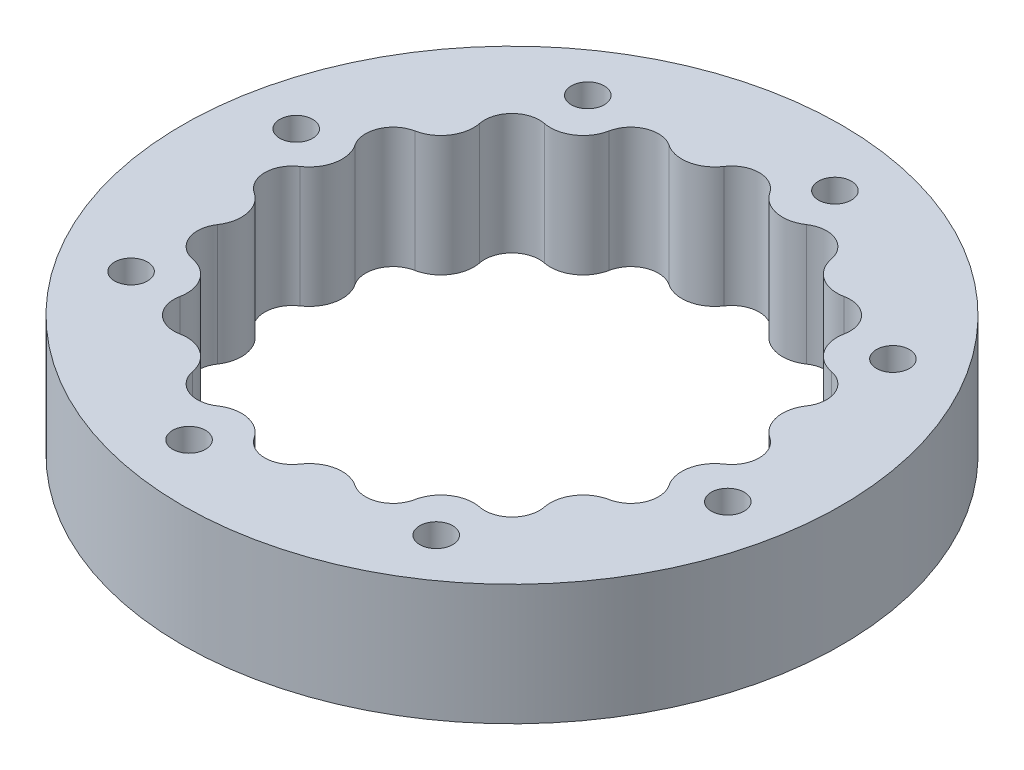
SolidWorks part; units mm, degrees
ref_plane "Front Plane" through (0, 0, 0) normal (0, 0, 1) x (1, 0, 0)
ref_plane "Top Plane" through (0, 0, 0) normal (0, 1, 0) x (1, 0, 0)
ref_plane "Right Plane" through (0, 0, 0) normal (1, 0, 0) x (0, 0, -1)
sketch "Sketch1" plane through (0, 0, 0) normal (0, 1, 0) x (1, 0, 0)
  arc A0 (-31.5919, 24.5347) -> (-34.7568, 19.7981) centre (0, 0) ccw
  arc A1 (4.9902, 39.6875) -> (-4.9902, 39.6875) centre (0, 40) ccw
  arc A2 (19.7981, 34.7568) -> (10.5774, 38.5761) centre (15.3073, 36.9552) ccw
  arc A3 (-31.5919, 24.5347) -> (-34.7568, 19.7981) centre (0, 0) ccw construction
  arc A4 (31.5919, 24.5347) -> (24.5347, 31.5919) centre (28.2843, 28.2843) ccw
  arc A5 (-31.5919, 24.5347) -> (-34.7568, 19.7981) centre (0, 0) ccw construction
  arc A6 (38.5761, 10.5774) -> (34.7568, 19.7981) centre (36.9552, 15.3073) ccw
  arc A7 (-31.5919, 24.5347) -> (-34.7568, 19.7981) centre (0, 0) ccw construction
  arc A8 (39.6875, -4.9902) -> (39.6875, 4.9902) centre (40, 0) ccw
  arc A9 (-31.5919, 24.5347) -> (-34.7568, 19.7981) centre (0, 0) ccw construction
  arc A10 (34.7568, -19.7981) -> (38.5761, -10.5774) centre (36.9552, -15.3073) ccw
  arc A11 (-31.5919, 24.5347) -> (-34.7568, 19.7981) centre (0, 0) ccw construction
  arc A12 (24.5347, -31.5919) -> (31.5919, -24.5347) centre (28.2843, -28.2843) ccw
  arc A13 (-31.5919, 24.5347) -> (-34.7568, 19.7981) centre (0, 0) ccw construction
  arc A14 (10.5774, -38.5761) -> (19.7981, -34.7568) centre (15.3073, -36.9552) ccw
  arc A15 (-31.5919, 24.5347) -> (-34.7568, 19.7981) centre (0, 0) ccw construction
  arc A16 (-4.9902, -39.6875) -> (4.9902, -39.6875) centre (0, -40) ccw
  arc A17 (-31.5919, 24.5347) -> (-34.7568, 19.7981) centre (0, 0) ccw construction
  arc A18 (-19.7981, -34.7568) -> (-10.5774, -38.5761) centre (-15.3073, -36.9552) ccw
  arc A19 (-31.5919, 24.5347) -> (-34.7568, 19.7981) centre (0, 0) ccw construction
  arc A20 (-31.5919, -24.5347) -> (-24.5347, -31.5919) centre (-28.2843, -28.2843) ccw
  arc A21 (-31.5919, 24.5347) -> (-34.7568, 19.7981) centre (0, 0) ccw construction
  arc A22 (-38.5761, -10.5774) -> (-34.7568, -19.7981) centre (-36.9552, -15.3073) ccw
  arc A23 (-31.5919, 24.5347) -> (-34.7568, 19.7981) centre (0, 0) ccw construction
  arc A24 (-39.6875, 4.9902) -> (-39.6875, -4.9902) centre (-40, 0) ccw
  arc A25 (-31.5919, 24.5347) -> (-34.7568, 19.7981) centre (0, 0) ccw construction
  arc A26 (-34.7568, 19.7981) -> (-38.5761, 10.5774) centre (-36.9552, 15.3073) ccw
  arc A27 (-31.5919, 24.5347) -> (-34.7568, 19.7981) centre (0, 0) ccw construction
  arc A28 (-24.5347, 31.5919) -> (-31.5919, 24.5347) centre (-28.2843, 28.2843) ccw
  arc A29 (-31.5919, 24.5347) -> (-34.7568, 19.7981) centre (0, 0) ccw construction
  arc A30 (-10.5774, 38.5761) -> (-19.7981, 34.7568) centre (-15.3073, 36.9552) ccw
  arc A31 (-31.5919, 24.5347) -> (-34.7568, 19.7981) centre (0, 0) ccw construction
  circle A32 centre (0, 0) radius 60
  arc A33 (-19.7981, 34.7568) -> (-24.5347, 31.5919) centre (0, 0) ccw
  arc A34 (-19.7981, 34.7568) -> (-24.5347, 31.5919) centre (0, 0) ccw construction
  arc A35 (-19.7981, 34.7568) -> (-24.5347, 31.5919) centre (0, 0) ccw construction
  arc A36 (-19.7981, 34.7568) -> (-24.5347, 31.5919) centre (0, 0) ccw construction
  arc A37 (-19.7981, 34.7568) -> (-24.5347, 31.5919) centre (0, 0) ccw construction
  arc A38 (-19.7981, 34.7568) -> (-24.5347, 31.5919) centre (0, 0) ccw construction
  arc A39 (-19.7981, 34.7568) -> (-24.5347, 31.5919) centre (0, 0) ccw construction
  arc A40 (-19.7981, 34.7568) -> (-24.5347, 31.5919) centre (0, 0) ccw construction
  arc A41 (-19.7981, 34.7568) -> (-24.5347, 31.5919) centre (0, 0) ccw construction
  arc A42 (-19.7981, 34.7568) -> (-24.5347, 31.5919) centre (0, 0) ccw construction
  arc A43 (-19.7981, 34.7568) -> (-24.5347, 31.5919) centre (0, 0) ccw construction
  arc A44 (-19.7981, 34.7568) -> (-24.5347, 31.5919) centre (0, 0) ccw construction
  arc A45 (-19.7981, 34.7568) -> (-24.5347, 31.5919) centre (0, 0) ccw construction
  arc A46 (-19.7981, 34.7568) -> (-24.5347, 31.5919) centre (0, 0) ccw construction
  arc A47 (-19.7981, 34.7568) -> (-24.5347, 31.5919) centre (0, 0) ccw construction
  arc A48 (-19.7981, 34.7568) -> (-24.5347, 31.5919) centre (0, 0) ccw construction
  arc A49 (-4.9902, 39.6875) -> (-10.5774, 38.5761) centre (0, 0) ccw
  arc A50 (-4.9902, 39.6875) -> (-10.5774, 38.5761) centre (0, 0) ccw construction
  arc A51 (-4.9902, 39.6875) -> (-10.5774, 38.5761) centre (0, 0) ccw construction
  arc A52 (-4.9902, 39.6875) -> (-10.5774, 38.5761) centre (0, 0) ccw construction
  arc A53 (-4.9902, 39.6875) -> (-10.5774, 38.5761) centre (0, 0) ccw construction
  arc A54 (-4.9902, 39.6875) -> (-10.5774, 38.5761) centre (0, 0) ccw construction
  arc A55 (-4.9902, 39.6875) -> (-10.5774, 38.5761) centre (0, 0) ccw construction
  arc A56 (-4.9902, 39.6875) -> (-10.5774, 38.5761) centre (0, 0) ccw construction
  arc A57 (-4.9902, 39.6875) -> (-10.5774, 38.5761) centre (0, 0) ccw construction
  arc A58 (-4.9902, 39.6875) -> (-10.5774, 38.5761) centre (0, 0) ccw construction
  arc A59 (-4.9902, 39.6875) -> (-10.5774, 38.5761) centre (0, 0) ccw construction
  arc A60 (-4.9902, 39.6875) -> (-10.5774, 38.5761) centre (0, 0) ccw construction
  arc A61 (-4.9902, 39.6875) -> (-10.5774, 38.5761) centre (0, 0) ccw construction
  arc A62 (-4.9902, 39.6875) -> (-10.5774, 38.5761) centre (0, 0) ccw construction
  arc A63 (-4.9902, 39.6875) -> (-10.5774, 38.5761) centre (0, 0) ccw construction
  arc A64 (-4.9902, 39.6875) -> (-10.5774, 38.5761) centre (0, 0) ccw construction
  arc A65 (10.5774, 38.5761) -> (4.9902, 39.6875) centre (0, 0) ccw
  arc A66 (10.5774, 38.5761) -> (4.9902, 39.6875) centre (0, 0) ccw construction
  arc A67 (10.5774, 38.5761) -> (4.9902, 39.6875) centre (0, 0) ccw construction
  arc A68 (10.5774, 38.5761) -> (4.9902, 39.6875) centre (0, 0) ccw construction
  arc A69 (10.5774, 38.5761) -> (4.9902, 39.6875) centre (0, 0) ccw construction
  arc A70 (10.5774, 38.5761) -> (4.9902, 39.6875) centre (0, 0) ccw construction
  arc A71 (10.5774, 38.5761) -> (4.9902, 39.6875) centre (0, 0) ccw construction
  arc A72 (10.5774, 38.5761) -> (4.9902, 39.6875) centre (0, 0) ccw construction
  arc A73 (10.5774, 38.5761) -> (4.9902, 39.6875) centre (0, 0) ccw construction
  arc A74 (10.5774, 38.5761) -> (4.9902, 39.6875) centre (0, 0) ccw construction
  arc A75 (10.5774, 38.5761) -> (4.9902, 39.6875) centre (0, 0) ccw construction
  arc A76 (10.5774, 38.5761) -> (4.9902, 39.6875) centre (0, 0) ccw construction
  arc A77 (10.5774, 38.5761) -> (4.9902, 39.6875) centre (0, 0) ccw construction
  arc A78 (10.5774, 38.5761) -> (4.9902, 39.6875) centre (0, 0) ccw construction
  arc A79 (10.5774, 38.5761) -> (4.9902, 39.6875) centre (0, 0) ccw construction
  arc A80 (10.5774, 38.5761) -> (4.9902, 39.6875) centre (0, 0) ccw construction
  arc A81 (24.5347, 31.5919) -> (19.7981, 34.7568) centre (0, 0) ccw
  arc A82 (24.5347, 31.5919) -> (19.7981, 34.7568) centre (0, 0) ccw construction
  arc A83 (24.5347, 31.5919) -> (19.7981, 34.7568) centre (0, 0) ccw construction
  arc A84 (24.5347, 31.5919) -> (19.7981, 34.7568) centre (0, 0) ccw construction
  arc A85 (24.5347, 31.5919) -> (19.7981, 34.7568) centre (0, 0) ccw construction
  arc A86 (24.5347, 31.5919) -> (19.7981, 34.7568) centre (0, 0) ccw construction
  arc A87 (24.5347, 31.5919) -> (19.7981, 34.7568) centre (0, 0) ccw construction
  arc A88 (24.5347, 31.5919) -> (19.7981, 34.7568) centre (0, 0) ccw construction
  arc A89 (24.5347, 31.5919) -> (19.7981, 34.7568) centre (0, 0) ccw construction
  arc A90 (24.5347, 31.5919) -> (19.7981, 34.7568) centre (0, 0) ccw construction
  arc A91 (24.5347, 31.5919) -> (19.7981, 34.7568) centre (0, 0) ccw construction
  arc A92 (24.5347, 31.5919) -> (19.7981, 34.7568) centre (0, 0) ccw construction
  arc A93 (24.5347, 31.5919) -> (19.7981, 34.7568) centre (0, 0) ccw construction
  arc A94 (24.5347, 31.5919) -> (19.7981, 34.7568) centre (0, 0) ccw construction
  arc A95 (24.5347, 31.5919) -> (19.7981, 34.7568) centre (0, 0) ccw construction
  arc A96 (24.5347, 31.5919) -> (19.7981, 34.7568) centre (0, 0) ccw construction
  arc A97 (34.7568, 19.7981) -> (31.5919, 24.5347) centre (0, 0) ccw
  arc A98 (34.7568, 19.7981) -> (31.5919, 24.5347) centre (0, 0) ccw construction
  arc A99 (34.7568, 19.7981) -> (31.5919, 24.5347) centre (0, 0) ccw construction
  arc A100 (34.7568, 19.7981) -> (31.5919, 24.5347) centre (0, 0) ccw construction
  arc A101 (34.7568, 19.7981) -> (31.5919, 24.5347) centre (0, 0) ccw construction
  arc A102 (34.7568, 19.7981) -> (31.5919, 24.5347) centre (0, 0) ccw construction
  arc A103 (34.7568, 19.7981) -> (31.5919, 24.5347) centre (0, 0) ccw construction
  arc A104 (34.7568, 19.7981) -> (31.5919, 24.5347) centre (0, 0) ccw construction
  arc A105 (34.7568, 19.7981) -> (31.5919, 24.5347) centre (0, 0) ccw construction
  arc A106 (34.7568, 19.7981) -> (31.5919, 24.5347) centre (0, 0) ccw construction
  arc A107 (34.7568, 19.7981) -> (31.5919, 24.5347) centre (0, 0) ccw construction
  arc A108 (34.7568, 19.7981) -> (31.5919, 24.5347) centre (0, 0) ccw construction
  arc A109 (34.7568, 19.7981) -> (31.5919, 24.5347) centre (0, 0) ccw construction
  arc A110 (34.7568, 19.7981) -> (31.5919, 24.5347) centre (0, 0) ccw construction
  arc A111 (34.7568, 19.7981) -> (31.5919, 24.5347) centre (0, 0) ccw construction
  arc A112 (34.7568, 19.7981) -> (31.5919, 24.5347) centre (0, 0) ccw construction
  arc A113 (39.6875, 4.9902) -> (38.5761, 10.5774) centre (0, 0) ccw
  arc A114 (39.6875, 4.9902) -> (38.5761, 10.5774) centre (0, 0) ccw construction
  arc A115 (39.6875, 4.9902) -> (38.5761, 10.5774) centre (0, 0) ccw construction
  arc A116 (39.6875, 4.9902) -> (38.5761, 10.5774) centre (0, 0) ccw construction
  arc A117 (39.6875, 4.9902) -> (38.5761, 10.5774) centre (0, 0) ccw construction
  arc A118 (39.6875, 4.9902) -> (38.5761, 10.5774) centre (0, 0) ccw construction
  arc A119 (39.6875, 4.9902) -> (38.5761, 10.5774) centre (0, 0) ccw construction
  arc A120 (39.6875, 4.9902) -> (38.5761, 10.5774) centre (0, 0) ccw construction
  arc A121 (39.6875, 4.9902) -> (38.5761, 10.5774) centre (0, 0) ccw construction
  arc A122 (39.6875, 4.9902) -> (38.5761, 10.5774) centre (0, 0) ccw construction
  arc A123 (39.6875, 4.9902) -> (38.5761, 10.5774) centre (0, 0) ccw construction
  arc A124 (39.6875, 4.9902) -> (38.5761, 10.5774) centre (0, 0) ccw construction
  arc A125 (39.6875, 4.9902) -> (38.5761, 10.5774) centre (0, 0) ccw construction
  arc A126 (39.6875, 4.9902) -> (38.5761, 10.5774) centre (0, 0) ccw construction
  arc A127 (39.6875, 4.9902) -> (38.5761, 10.5774) centre (0, 0) ccw construction
  arc A128 (39.6875, 4.9902) -> (38.5761, 10.5774) centre (0, 0) ccw construction
  arc A129 (38.5761, -10.5774) -> (39.6875, -4.9902) centre (0, 0) ccw
  arc A130 (38.5761, -10.5774) -> (39.6875, -4.9902) centre (0, 0) ccw construction
  arc A131 (38.5761, -10.5774) -> (39.6875, -4.9902) centre (0, 0) ccw construction
  arc A132 (38.5761, -10.5774) -> (39.6875, -4.9902) centre (0, 0) ccw construction
  arc A133 (38.5761, -10.5774) -> (39.6875, -4.9902) centre (0, 0) ccw construction
  arc A134 (38.5761, -10.5774) -> (39.6875, -4.9902) centre (0, 0) ccw construction
  arc A135 (38.5761, -10.5774) -> (39.6875, -4.9902) centre (0, 0) ccw construction
  arc A136 (38.5761, -10.5774) -> (39.6875, -4.9902) centre (0, 0) ccw construction
  arc A137 (38.5761, -10.5774) -> (39.6875, -4.9902) centre (0, 0) ccw construction
  arc A138 (38.5761, -10.5774) -> (39.6875, -4.9902) centre (0, 0) ccw construction
  arc A139 (38.5761, -10.5774) -> (39.6875, -4.9902) centre (0, 0) ccw construction
  arc A140 (38.5761, -10.5774) -> (39.6875, -4.9902) centre (0, 0) ccw construction
  arc A141 (38.5761, -10.5774) -> (39.6875, -4.9902) centre (0, 0) ccw construction
  arc A142 (38.5761, -10.5774) -> (39.6875, -4.9902) centre (0, 0) ccw construction
  arc A143 (38.5761, -10.5774) -> (39.6875, -4.9902) centre (0, 0) ccw construction
  arc A144 (38.5761, -10.5774) -> (39.6875, -4.9902) centre (0, 0) ccw construction
  arc A145 (31.5919, -24.5347) -> (34.7568, -19.7981) centre (0, 0) ccw
  arc A146 (31.5919, -24.5347) -> (34.7568, -19.7981) centre (0, 0) ccw construction
  arc A147 (31.5919, -24.5347) -> (34.7568, -19.7981) centre (0, 0) ccw construction
  arc A148 (31.5919, -24.5347) -> (34.7568, -19.7981) centre (0, 0) ccw construction
  arc A149 (31.5919, -24.5347) -> (34.7568, -19.7981) centre (0, 0) ccw construction
  arc A150 (31.5919, -24.5347) -> (34.7568, -19.7981) centre (0, 0) ccw construction
  arc A151 (31.5919, -24.5347) -> (34.7568, -19.7981) centre (0, 0) ccw construction
  arc A152 (31.5919, -24.5347) -> (34.7568, -19.7981) centre (0, 0) ccw construction
  arc A153 (31.5919, -24.5347) -> (34.7568, -19.7981) centre (0, 0) ccw construction
  arc A154 (31.5919, -24.5347) -> (34.7568, -19.7981) centre (0, 0) ccw construction
  arc A155 (31.5919, -24.5347) -> (34.7568, -19.7981) centre (0, 0) ccw construction
  arc A156 (31.5919, -24.5347) -> (34.7568, -19.7981) centre (0, 0) ccw construction
  arc A157 (31.5919, -24.5347) -> (34.7568, -19.7981) centre (0, 0) ccw construction
  arc A158 (31.5919, -24.5347) -> (34.7568, -19.7981) centre (0, 0) ccw construction
  arc A159 (31.5919, -24.5347) -> (34.7568, -19.7981) centre (0, 0) ccw construction
  arc A160 (31.5919, -24.5347) -> (34.7568, -19.7981) centre (0, 0) ccw construction
  arc A161 (19.7981, -34.7568) -> (24.5347, -31.5919) centre (0, 0) ccw
  arc A162 (19.7981, -34.7568) -> (24.5347, -31.5919) centre (0, 0) ccw construction
  arc A163 (19.7981, -34.7568) -> (24.5347, -31.5919) centre (0, 0) ccw construction
  arc A164 (19.7981, -34.7568) -> (24.5347, -31.5919) centre (0, 0) ccw construction
  arc A165 (19.7981, -34.7568) -> (24.5347, -31.5919) centre (0, 0) ccw construction
  arc A166 (19.7981, -34.7568) -> (24.5347, -31.5919) centre (0, 0) ccw construction
  arc A167 (19.7981, -34.7568) -> (24.5347, -31.5919) centre (0, 0) ccw construction
  arc A168 (19.7981, -34.7568) -> (24.5347, -31.5919) centre (0, 0) ccw construction
  arc A169 (19.7981, -34.7568) -> (24.5347, -31.5919) centre (0, 0) ccw construction
  arc A170 (19.7981, -34.7568) -> (24.5347, -31.5919) centre (0, 0) ccw construction
  arc A171 (19.7981, -34.7568) -> (24.5347, -31.5919) centre (0, 0) ccw construction
  arc A172 (19.7981, -34.7568) -> (24.5347, -31.5919) centre (0, 0) ccw construction
  arc A173 (19.7981, -34.7568) -> (24.5347, -31.5919) centre (0, 0) ccw construction
  arc A174 (19.7981, -34.7568) -> (24.5347, -31.5919) centre (0, 0) ccw construction
  arc A175 (19.7981, -34.7568) -> (24.5347, -31.5919) centre (0, 0) ccw construction
  arc A176 (19.7981, -34.7568) -> (24.5347, -31.5919) centre (0, 0) ccw construction
  arc A177 (4.9902, -39.6875) -> (10.5774, -38.5761) centre (0, 0) ccw
  arc A178 (4.9902, -39.6875) -> (10.5774, -38.5761) centre (0, 0) ccw construction
  arc A179 (4.9902, -39.6875) -> (10.5774, -38.5761) centre (0, 0) ccw construction
  arc A180 (4.9902, -39.6875) -> (10.5774, -38.5761) centre (0, 0) ccw construction
  arc A181 (4.9902, -39.6875) -> (10.5774, -38.5761) centre (0, 0) ccw construction
  arc A182 (4.9902, -39.6875) -> (10.5774, -38.5761) centre (0, 0) ccw construction
  arc A183 (4.9902, -39.6875) -> (10.5774, -38.5761) centre (0, 0) ccw construction
  arc A184 (4.9902, -39.6875) -> (10.5774, -38.5761) centre (0, 0) ccw construction
  arc A185 (4.9902, -39.6875) -> (10.5774, -38.5761) centre (0, 0) ccw construction
  arc A186 (4.9902, -39.6875) -> (10.5774, -38.5761) centre (0, 0) ccw construction
  arc A187 (4.9902, -39.6875) -> (10.5774, -38.5761) centre (0, 0) ccw construction
  arc A188 (4.9902, -39.6875) -> (10.5774, -38.5761) centre (0, 0) ccw construction
  arc A189 (4.9902, -39.6875) -> (10.5774, -38.5761) centre (0, 0) ccw construction
  arc A190 (4.9902, -39.6875) -> (10.5774, -38.5761) centre (0, 0) ccw construction
  arc A191 (4.9902, -39.6875) -> (10.5774, -38.5761) centre (0, 0) ccw construction
  arc A192 (4.9902, -39.6875) -> (10.5774, -38.5761) centre (0, 0) ccw construction
  arc A193 (-10.5774, -38.5761) -> (-4.9902, -39.6875) centre (0, 0) ccw
  arc A194 (-10.5774, -38.5761) -> (-4.9902, -39.6875) centre (0, 0) ccw construction
  arc A195 (-10.5774, -38.5761) -> (-4.9902, -39.6875) centre (0, 0) ccw construction
  arc A196 (-10.5774, -38.5761) -> (-4.9902, -39.6875) centre (0, 0) ccw construction
  arc A197 (-10.5774, -38.5761) -> (-4.9902, -39.6875) centre (0, 0) ccw construction
  arc A198 (-10.5774, -38.5761) -> (-4.9902, -39.6875) centre (0, 0) ccw construction
  arc A199 (-10.5774, -38.5761) -> (-4.9902, -39.6875) centre (0, 0) ccw construction
  arc A200 (-10.5774, -38.5761) -> (-4.9902, -39.6875) centre (0, 0) ccw construction
  arc A201 (-10.5774, -38.5761) -> (-4.9902, -39.6875) centre (0, 0) ccw construction
  arc A202 (-10.5774, -38.5761) -> (-4.9902, -39.6875) centre (0, 0) ccw construction
  arc A203 (-10.5774, -38.5761) -> (-4.9902, -39.6875) centre (0, 0) ccw construction
  arc A204 (-10.5774, -38.5761) -> (-4.9902, -39.6875) centre (0, 0) ccw construction
  arc A205 (-10.5774, -38.5761) -> (-4.9902, -39.6875) centre (0, 0) ccw construction
  arc A206 (-10.5774, -38.5761) -> (-4.9902, -39.6875) centre (0, 0) ccw construction
  arc A207 (-10.5774, -38.5761) -> (-4.9902, -39.6875) centre (0, 0) ccw construction
  arc A208 (-10.5774, -38.5761) -> (-4.9902, -39.6875) centre (0, 0) ccw construction
  arc A209 (-24.5347, -31.5919) -> (-19.7981, -34.7568) centre (0, 0) ccw
  arc A210 (-24.5347, -31.5919) -> (-19.7981, -34.7568) centre (0, 0) ccw construction
  arc A211 (-24.5347, -31.5919) -> (-19.7981, -34.7568) centre (0, 0) ccw construction
  arc A212 (-24.5347, -31.5919) -> (-19.7981, -34.7568) centre (0, 0) ccw construction
  arc A213 (-24.5347, -31.5919) -> (-19.7981, -34.7568) centre (0, 0) ccw construction
  arc A214 (-24.5347, -31.5919) -> (-19.7981, -34.7568) centre (0, 0) ccw construction
  arc A215 (-24.5347, -31.5919) -> (-19.7981, -34.7568) centre (0, 0) ccw construction
  arc A216 (-24.5347, -31.5919) -> (-19.7981, -34.7568) centre (0, 0) ccw construction
  arc A217 (-24.5347, -31.5919) -> (-19.7981, -34.7568) centre (0, 0) ccw construction
  arc A218 (-24.5347, -31.5919) -> (-19.7981, -34.7568) centre (0, 0) ccw construction
  arc A219 (-24.5347, -31.5919) -> (-19.7981, -34.7568) centre (0, 0) ccw construction
  arc A220 (-24.5347, -31.5919) -> (-19.7981, -34.7568) centre (0, 0) ccw construction
  arc A221 (-24.5347, -31.5919) -> (-19.7981, -34.7568) centre (0, 0) ccw construction
  arc A222 (-24.5347, -31.5919) -> (-19.7981, -34.7568) centre (0, 0) ccw construction
  arc A223 (-24.5347, -31.5919) -> (-19.7981, -34.7568) centre (0, 0) ccw construction
  arc A224 (-24.5347, -31.5919) -> (-19.7981, -34.7568) centre (0, 0) ccw construction
  arc A225 (-34.7568, -19.7981) -> (-31.5919, -24.5347) centre (0, 0) ccw
  arc A226 (-34.7568, -19.7981) -> (-31.5919, -24.5347) centre (0, 0) ccw construction
  arc A227 (-34.7568, -19.7981) -> (-31.5919, -24.5347) centre (0, 0) ccw construction
  arc A228 (-34.7568, -19.7981) -> (-31.5919, -24.5347) centre (0, 0) ccw construction
  arc A229 (-34.7568, -19.7981) -> (-31.5919, -24.5347) centre (0, 0) ccw construction
  arc A230 (-34.7568, -19.7981) -> (-31.5919, -24.5347) centre (0, 0) ccw construction
  arc A231 (-34.7568, -19.7981) -> (-31.5919, -24.5347) centre (0, 0) ccw construction
  arc A232 (-34.7568, -19.7981) -> (-31.5919, -24.5347) centre (0, 0) ccw construction
  arc A233 (-34.7568, -19.7981) -> (-31.5919, -24.5347) centre (0, 0) ccw construction
  arc A234 (-34.7568, -19.7981) -> (-31.5919, -24.5347) centre (0, 0) ccw construction
  arc A235 (-34.7568, -19.7981) -> (-31.5919, -24.5347) centre (0, 0) ccw construction
  arc A236 (-34.7568, -19.7981) -> (-31.5919, -24.5347) centre (0, 0) ccw construction
  arc A237 (-34.7568, -19.7981) -> (-31.5919, -24.5347) centre (0, 0) ccw construction
  arc A238 (-34.7568, -19.7981) -> (-31.5919, -24.5347) centre (0, 0) ccw construction
  arc A239 (-34.7568, -19.7981) -> (-31.5919, -24.5347) centre (0, 0) ccw construction
  arc A240 (-34.7568, -19.7981) -> (-31.5919, -24.5347) centre (0, 0) ccw construction
  arc A241 (-39.6875, -4.9902) -> (-38.5761, -10.5774) centre (0, 0) ccw
  arc A242 (-39.6875, -4.9902) -> (-38.5761, -10.5774) centre (0, 0) ccw construction
  arc A243 (-39.6875, -4.9902) -> (-38.5761, -10.5774) centre (0, 0) ccw construction
  arc A244 (-39.6875, -4.9902) -> (-38.5761, -10.5774) centre (0, 0) ccw construction
  arc A245 (-39.6875, -4.9902) -> (-38.5761, -10.5774) centre (0, 0) ccw construction
  arc A246 (-39.6875, -4.9902) -> (-38.5761, -10.5774) centre (0, 0) ccw construction
  arc A247 (-39.6875, -4.9902) -> (-38.5761, -10.5774) centre (0, 0) ccw construction
  arc A248 (-39.6875, -4.9902) -> (-38.5761, -10.5774) centre (0, 0) ccw construction
  arc A249 (-39.6875, -4.9902) -> (-38.5761, -10.5774) centre (0, 0) ccw construction
  arc A250 (-39.6875, -4.9902) -> (-38.5761, -10.5774) centre (0, 0) ccw construction
  arc A251 (-39.6875, -4.9902) -> (-38.5761, -10.5774) centre (0, 0) ccw construction
  arc A252 (-39.6875, -4.9902) -> (-38.5761, -10.5774) centre (0, 0) ccw construction
  arc A253 (-39.6875, -4.9902) -> (-38.5761, -10.5774) centre (0, 0) ccw construction
  arc A254 (-39.6875, -4.9902) -> (-38.5761, -10.5774) centre (0, 0) ccw construction
  arc A255 (-39.6875, -4.9902) -> (-38.5761, -10.5774) centre (0, 0) ccw construction
  arc A256 (-39.6875, -4.9902) -> (-38.5761, -10.5774) centre (0, 0) ccw construction
  arc A257 (-38.5761, 10.5774) -> (-39.6875, 4.9902) centre (0, 0) ccw
  arc A258 (-38.5761, 10.5774) -> (-39.6875, 4.9902) centre (0, 0) ccw construction
  arc A259 (-38.5761, 10.5774) -> (-39.6875, 4.9902) centre (0, 0) ccw construction
  arc A260 (-38.5761, 10.5774) -> (-39.6875, 4.9902) centre (0, 0) ccw construction
  arc A261 (-38.5761, 10.5774) -> (-39.6875, 4.9902) centre (0, 0) ccw construction
  arc A262 (-38.5761, 10.5774) -> (-39.6875, 4.9902) centre (0, 0) ccw construction
  arc A263 (-38.5761, 10.5774) -> (-39.6875, 4.9902) centre (0, 0) ccw construction
  arc A264 (-38.5761, 10.5774) -> (-39.6875, 4.9902) centre (0, 0) ccw construction
  arc A265 (-38.5761, 10.5774) -> (-39.6875, 4.9902) centre (0, 0) ccw construction
  arc A266 (-38.5761, 10.5774) -> (-39.6875, 4.9902) centre (0, 0) ccw construction
  arc A267 (-38.5761, 10.5774) -> (-39.6875, 4.9902) centre (0, 0) ccw construction
  arc A268 (-38.5761, 10.5774) -> (-39.6875, 4.9902) centre (0, 0) ccw construction
  arc A269 (-38.5761, 10.5774) -> (-39.6875, 4.9902) centre (0, 0) ccw construction
  arc A270 (-38.5761, 10.5774) -> (-39.6875, 4.9902) centre (0, 0) ccw construction
  arc A271 (-38.5761, 10.5774) -> (-39.6875, 4.9902) centre (0, 0) ccw construction
  arc A272 (-38.5761, 10.5774) -> (-39.6875, 4.9902) centre (0, 0) ccw construction
  point P52 (0, 0)
  dimension "D1" = 80
  dimension "D2" = 10
  dimension "D4" = 120
  dimension "D3" = 16
extrude "Boss-Extrude1" add sketch "Sketch1" along normal blind 22
fillet "Fillet1" radius 5 32 edges at (-31.5919, 11, -24.5347) (-34.7568, 11, -19.7981) (10.5774, 11, 38.5761) (4.9902, 11, 39.6875) (-4.9902, 11, 39.6875) (-10.5774, 11, 38.5761) (-19.7981, 11, 34.7568) (-24.5347, 11, 31.5919) (-31.5919, 11, 24.5347) (-34.7568, 11, 19.7981) (-38.5761, 11, 10.5774) (-39.6875, 11, 4.9902) (-39.6875, 11, -4.9902) (-38.5761, 11, -10.5774) (19.7981, 11, 34.7568) (24.5347, 11, 31.5919) (31.5919, 11, 24.5347) (34.7568, 11, 19.7981) (38.5761, 11, 10.5774) (39.6875, 11, 4.9902) (39.6875, 11, -4.9902) (38.5761, 11, -10.5774) (34.7568, 11, -19.7981) (31.5919, 11, -24.5347) (24.5347, 11, -31.5919) (19.7981, 11, -34.7568) (10.5774, 11, -38.5761) (4.9902, 11, -39.6875) (-4.9902, 11, -39.6875) (-10.5774, 11, -38.5761) (-19.7981, 11, -34.7568) (-24.5347, 11, -31.5919)
fillet "Fillet2" radius 6 16 edges at (-7.8059, 11, 39.2431) (7.8059, 11, 39.2431) (22.2294, 11, 33.2687) (33.2687, 11, 22.2294) (-22.2294, 11, 33.2687) (-33.2687, 11, 22.2294) (-39.2431, 11, 7.8059) (-39.2431, 11, -7.8059) (39.2431, 11, 7.8059) (39.2431, 11, -7.8059) (33.2687, 11, -22.2294) (22.2294, 11, -33.2687) (7.8059, 11, -39.2431) (-7.8059, 11, -39.2431) (-22.2294, 11, -33.2687) (-33.2687, 11, -22.2294)
sketch "Sketch3" plane through (0, 22, 0) normal (0, 1, 0) x (1, 0, 0)
  line L0 (7.9956, 40.1966) -> (11.7054, 58.8471) construction
  circle A0 centre (0, 0) radius 50 construction
  circle A4 centre (9.7545, 49.0393) radius 3
  arc A5 (4.1664, 42.7642) -> (12.5159, 41.1034) centre (9.1661, 46.0813) ccw construction
  circle A6 centre (0, 0) radius 60 construction
  circle A7 centre (41.5735, 27.7785) radius 3
  circle A8 centre (49.0393, -9.7545) radius 3
  circle A9 centre (27.7785, -41.5735) radius 3
  circle A10 centre (-9.7545, -49.0393) radius 3
  circle A11 centre (-41.5735, -27.7785) radius 3
  circle A12 centre (-49.0393, 9.7545) radius 3
  circle A13 centre (-27.7785, 41.5735) radius 3
  point P12 (0, 0)
  point P13 (9.1661, 46.0813)
  point P14 (0, 0)
  point P16 (41.5735, 27.7785)
  point P31 (0, 0)
  dimension "D1" = 100
  dimension "D2" = 6
  dimension "D3" = 8
extrude "Cut-Extrude1" cut sketch "Sketch3" against normal through all
equation "\"R_ROLL\"= 5mm"
equation "\"D_SUN\"= 80mm"
equation "\"NUM_ROLL\"= 16"
equation "\"RHO\"= 1mm"
equation "\"D_SHAFT\"= 15mm"
equation "\"D_OUTPUT\"= 40mm"
equation "\"NUM_OUT\"= 6"
equation "\"R_OUT_ROLL\"= 5mm"
equation "\"D1@Sketch1\"=\"D_SUN\""
equation "\"D2@Sketch1\"=\"R_ROLL\"*2"
equation "\"D3@Sketch1\"=\"NUM_ROLL\""
equation "\"D4@Sketch1\"=\"D_SUN\"+40"
